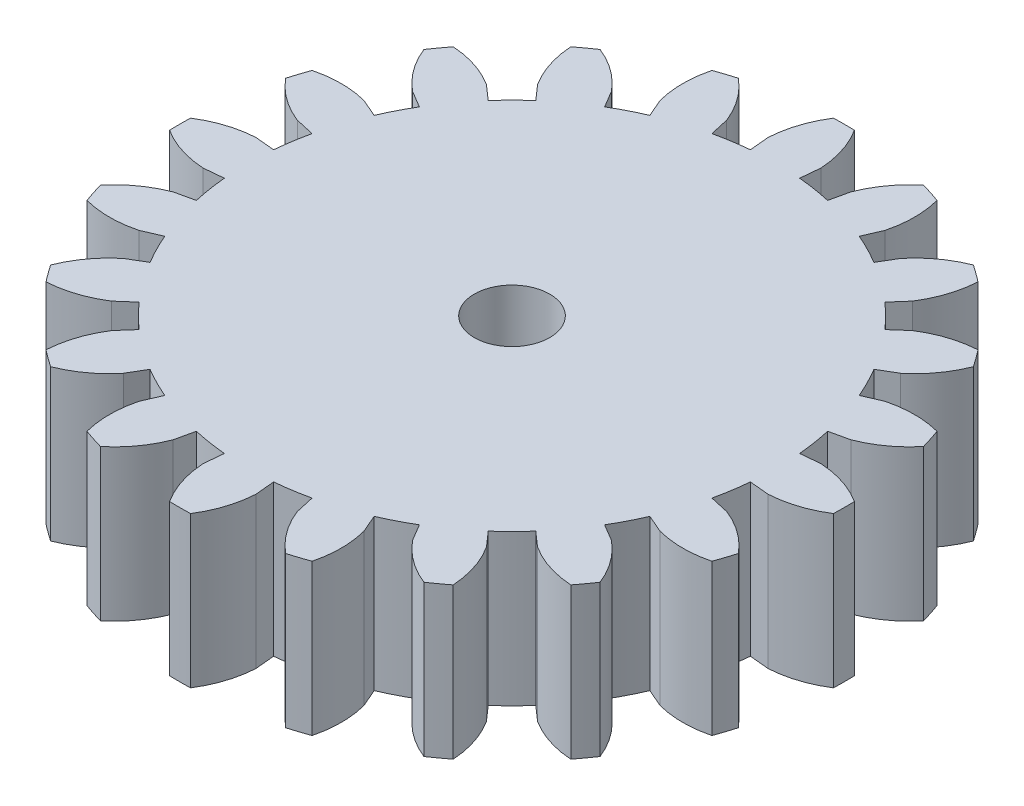
SolidWorks part; units mm, degrees
ref_plane "Спереди" through (0, 0, 0) normal (0, 0, 1) x (1, 0, 0)
ref_plane "Сверху" through (0, 0, 0) normal (0, 1, 0) x (1, 0, 0)
ref_plane "Справа" through (0, 0, 0) normal (1, 0, 0) x (0, 0, -1)
other "Configuration Table"
sketch "Эскиз1" plane through (0, 0, 0) normal (0, 1, 0) x (1, 0, 0)
  circle A0 centre (0, 0) radius 17.5
  dimension "D1" = 35
extrude "Бобышка-Вытянуть1" add sketch "Эскиз1" along normal blind 10
sketch "Эскиз2" plane through (0, 0, 0) normal (0, -1, 0) x (1, 0, 0)
  line L0 (0, 0) -> (0, 22) construction
  line L1 (0, 0) -> (-1.7523, 18.712) construction
  line L2 (0, 0) -> (1.7523, 18.712) construction
  line L5 (-1.5692, 19.9383) -> (0, 0) construction
  line L6 (0, 0) -> (1.5692, 19.9383) construction
  line L7 (-0.6949, 21.989) -> (0, 0) construction
  line L8 (-1.6317, 17.4238) -> (-1.7523, 18.712)
  line L9 (1.7523, 18.712) -> (1.6317, 17.4238)
  circle A0 centre (0, 0) radius 18.7938 construction
  circle A1 centre (0, 0) radius 20 construction
  circle A2 centre (0, 0) radius 22 construction
  arc A3 (-0.6949, 21.989) -> (0.6949, 21.989) centre (0, 0) cw
  arc A4 (-1.6317, 17.4238) -> (1.6317, 17.4238) centre (0, 0) cw
  circle A5 centre (0, 0) radius 17.5 construction
  arc A6 (-1.5692, 19.9383) -> (1.5692, 19.9383) centre (0, 0) cw construction
  arc A7 (-1.7523, 18.712) -> (-0.6949, 21.989) centre (5.0681, 18.3203) cw
  arc A8 (0.6949, 21.989) -> (1.7523, 18.712) centre (-5.0681, 18.3203) cw
  point P12 (0, 20)
  point P16 (0, 22)
  point P22 (0, 17.5)
  dimension "D1" = 37.5877
  dimension "D2" = 40
  dimension "D3" = 44
  dimension "D4" = 5.35
  dimension "D5" = 4.5
  dimension "D6" = 1.81
extrude "Бобышка-Вытянуть2" add sketch "Эскиз2" against normal blind 10
pattern_circular "Круговой массив1" count 20 over 360 about axis through (0, 10, 0) along (0, -1, 0) of "Бобышка-Вытянуть2" reverse direction yes
sketch "Эскиз3" plane through (0, 0, 0) normal (0, -1, 0) x (1, 0, 0)
  circle A0 centre (0, 0) radius 2.5
  dimension "D1" = 5
extrude "Вырез-Вытянуть1" cut sketch "Эскиз3" against normal through all
equation "\"Ширина груза\"= 420"
equation "\"Глубина груза\"= 490"
equation "\"Высота груза\"= 297"
equation "\"Ширина ячейки\"= \"Ширина груза\" + 10"
equation "\"Глубина ячейки\"= \"Глубина груза\" + 10"
equation "\"Высота ячейки\"= \"Высота груза\" + 10 + 13"
equation "\"Колво ячеек ширина\"= 2"
equation "\"Колво ячеек высота\"= 2"
equation "\"Толщина стенки\"= 10"
equation "\"Крепление дверцы\"= 5"
equation "\"Ширина рейки\"= \"Толщина шестерни\""
equation "\"Высота рейки\"= 20"
equation "\"Высота пола\"= 20"
equation "\"Колво полозьев\"= 5"
equation "\"Отступ рейки\"= 20"
equation "\"Глубина каретки\"= \"Глубина ячейки\" + 30 + \"Мотор Y высота корпуса\" + 20"
equation "\"Длинна рейки\"= ( \"Ширина ячейки\" + \"Толщина стенки\" + \"Крепление дверцы\" ) * \"Колво ячеек ширина\" + \"Ширина ячейки выгрузки\" * \"Колво выгрузки\" + \"Толщина стенки\""
equation "\"Отступ шпильки\"= 26"
equation "\"Диаметр шпильки\"= 5"
equation "\"Длинна шпильки\"= ( \"Высота ячейки\" + \"Толщина стенки\" + \"Высота пола\" ) * \"Колво ячеек высота\" + ( \"Толщина стенки\" + \"Отступ рейки\" ) * 2 "
equation "\"Ширина пластины\"= 50  "
equation "\"Высота зона выгрузки\"= \"Высота ячейки\" * 2 + \"Толщина стенки\" * 2"
equation "\"Колво выгрузки\"= 1"
equation "\"Ширина ячейки выгрузки\"= \"Ширина ячейки\" + \"Толщина стенки\" + \"Отступ крепления мотора фиксации\"*2"
equation "\"Отступ крепления мотора фиксации\" = 30"
equation "\"Мотор X ширина корпуса\"= 42.3"
equation "\"Мотор X высота корпуса\"= 42.3"
equation "\"Мотор X длина корпуса\"= 40"
equation "\"Мотор X вылет вала\"= 19.8"
equation "\"Мотор Y ширина корпуса\"= 42.3"
equation "\"Мотор Y высота корпуса\"= 42.3"
equation "\"Мотор Y длина корпуса\"= 48"
equation "\"Мотор Y вылет вала\"= 30"
equation "\"Мотор Z ширина корпуса\"= 42"
equation "\"Мотор Z высота корпуса\"= 42"
equation "\"Мотор Z длина корпуса\"= 40"
equation "\"Мотор Z вылет вала\"= 23"
equation "\"Мотор диаметр вала ПРЕДВ\"= 5"
equation "\"Мотор шаг крепления ПРЕДВ\"= 31"
equation "\"Мотор диаметр отверстий ПРЕДВ\"= 3"
equation "\"Мотор глубина отверстий ПРЕДВ\"= 4.5"
equation "\"Мотор диаметр буртика ПРЕДВ\"= 22"
equation "\"Мотор высота буртика ПРЕДВ\"= 2"
equation "\"Мотор диаметр шкива ПРЕДВ\"= 16"
equation "\"Мотор длина шкива ПРЕДВ\"= 12"
equation "\"Мотор отступ шкива ПРЕДВ\"= 5"
equation "\"Мотор X шаг градусов\"= 1.8"
equation "\"Мотор Y шаг градусов\"= 1.8"
equation "\"Мотор Z шаг градусов\"= 1.8"
equation "\"Мотор Y диаметр ротора\"= 25.78"
equation "\"Толщина шестерни\"= 10"
equation "\"D1@Бобышка-Вытянуть1\"=\"Толщина шестерни\""
equation "\"D1@Бобышка-Вытянуть2\"=\"Толщина шестерни\""
equation "\"D1@Эскиз3\"=\"Мотор диаметр вала ПРЕДВ\""
